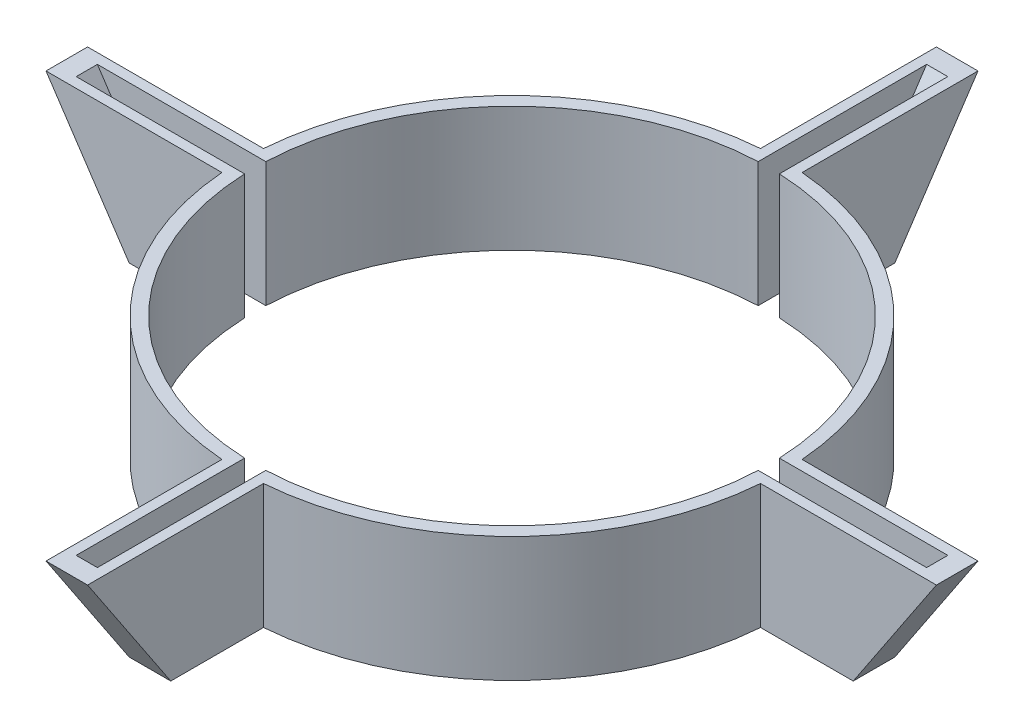
SolidWorks part; units mm, degrees
ref_plane "Front Plane" through (0, 0, 0) normal (0, 0, 1) x (1, 0, 0)
ref_plane "Top Plane" through (0, 0, 0) normal (0, 1, 0) x (1, 0, 0)
ref_plane "Right Plane" through (0, 0, 0) normal (1, 0, 0) x (0, 0, -1)
sketch "Sketch1" plane through (0, 0, 0) normal (0, 1, 0) x (1, 0, 0)
  circle A0 centre (0, 0) radius 39.243
  circle A1 centre (0, 0) radius 41.243
  dimension "D1" = 78.486
  dimension "D2" = 2
extrude "Boss-Extrude1" add sketch "Sketch1" along normal mid plane 114.3
sketch "Sketch2" plane through (0, 0, 0) normal (1, 0, 0) x (0, 0, -1)
  line L0 (41.243, 57.15) -> (41.243, -44.45) construction
  line L1 (41.243, -57.15) -> (41.243, 57.15) construction
  line L2 (41.243, 57.15) -> (108.9762, 57.15) construction
  line L3 (108.9762, 57.15) -> (41.243, -44.45) construction
  point P5 (79.1906, 57.15)
  dimension "D1" = 101.6
  dimension "D2" = 33.69
ref_plane "Plane1" through (0, -44.45, -41.243) normal (0, 0, -1) x (-1, 0, 0)
sketch "Sketch3" plane through (0, -44.45, -41.243) normal (0, 0, -1) x (-1, 0, 0)
  line L0 (-10.0825, 0) -> (10.0825, 0) construction
  point P3 (0, 0)
ref_plane "Plane2" through (0, -32.7121, -49.0683) normal (0, 0.5547, 0.8321) x (1, 0, 0)
sketch "Sketch4" plane through (0, -32.7121, -49.0683) normal (0, 0.5547, 0.8321) x (1, 0, 0)
  line L0 (3.175, -14.1072) -> (-3.175, -14.1072)
  line L1 (-3.175, -14.1072) -> (-3.175, 82.6007)
  line L2 (-3.175, 82.6007) -> (3.175, 82.6007)
  line L3 (3.175, 82.6007) -> (3.175, -14.1072)
  point P4 (0, -14.1072)
  dimension "D1" = 6.35
  dimension "D2" = 25.4
extrude "Boss-Extrude2" add sketch "Sketch4" along normal up to surface (64.6189 mm away) up to face at (0, 57.15, 41.243)
sketch "Sketch5" plane through (0, 68.728, -45.8185) normal (0, 0.8321, -0.5547) x (1, 0, 0)
  line L0 (0, 2.6152) -> (0, 58.9727) construction
  line L1 (-1.6192, -10.1336) -> (1.6193, -10.1336)
  line L2 (-1.6192, -10.1336) -> (-1.6192, 56.4327)
  line L3 (-1.6192, 56.4327) -> (1.6193, 56.4327)
  line L4 (1.6193, -10.1336) -> (1.6193, 56.4327)
  line L5 (-1.6192, -10.1336) -> (1.6193, 56.4327) construction
  line L6 (-1.6192, 56.4327) -> (1.6193, -10.1336) construction
  line L7 (3.175, 58.9727) -> (-3.175, 58.9727) construction
  point P0 (0, 23.1495)
  dimension "D1" = 3.2385
  dimension "D2" = 2.54
extrude "Cut-Extrude1" cut sketch "Sketch5" against normal up to surface (9.7384 mm away) up to face at (0, 57.15, 39.243)
pattern_circular "CirPattern1" count 4 over 360 about axis through (0, 57.15, 0) along (0, -1, 0) of "Cut-Extrude1", "Boss-Extrude2"
sketch "Sketch6" plane through (0, 0, 0) normal (1, 0, 0) x (0, 0, -1)
  line L1 (94.8868, 71.8599) -> (-94.8868, 71.8599)
  line L2 (94.8868, 71.8599) -> (94.8868, -4.3401)
  line L3 (94.8868, -4.3401) -> (-94.8868, -4.3401)
  line L4 (-94.8868, 71.8599) -> (-94.8868, -4.3401)
  line L5 (94.8868, -80.5401) -> (-94.8868, -80.5401)
  line L6 (94.8868, -80.5401) -> (94.8868, -23.3901)
  line L7 (94.8868, -23.3901) -> (-94.8868, -23.3901)
  line L8 (-94.8868, -80.5401) -> (-94.8868, -23.3901)
  point P9 (0, 0)
  dimension "D1" = 19.05
  dimension "D2" = 57.15
  dimension "D3" = 76.2
extrude "Cut-Extrude2" cut sketch "Sketch6" against normal through all both and the other way through all
